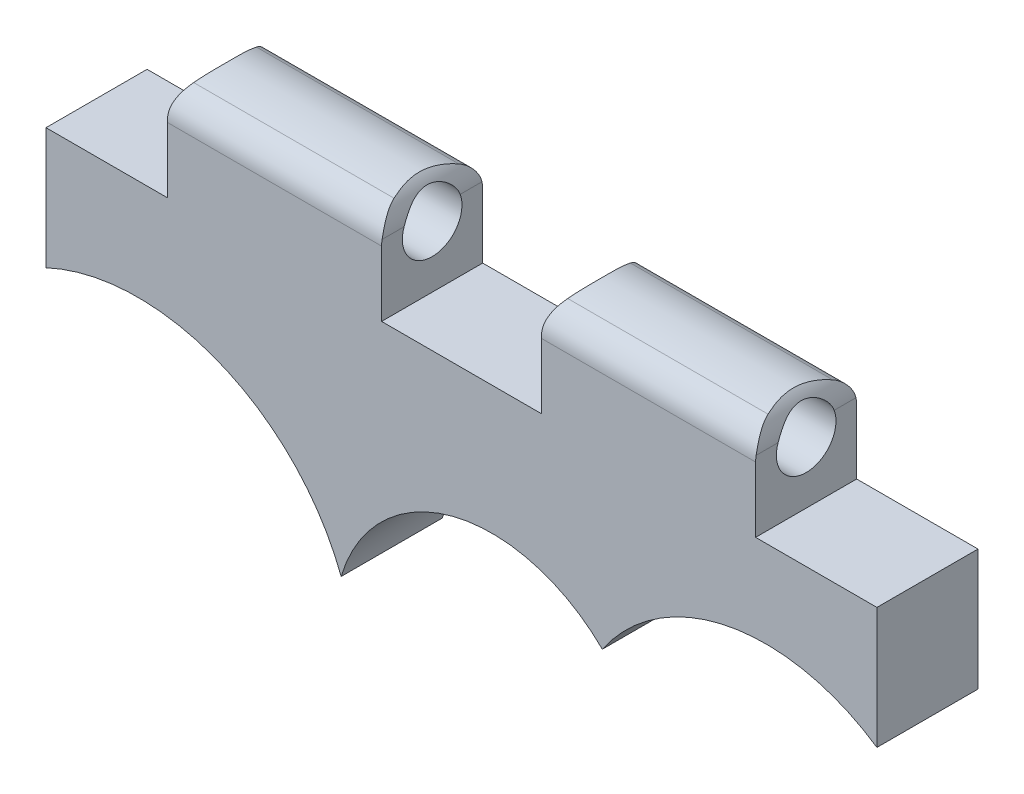
SolidWorks part; units mm, degrees
ref_plane "Alzado" through (0, 0, 0) normal (0, 0, 1) x (1, 0, 0)
ref_plane "Planta" through (0, 0, 0) normal (0, 1, 0) x (1, 0, 0)
ref_plane "Vista lateral" through (0, 0, 0) normal (1, 0, 0) x (0, 0, -1)
sketch "Croquis1" plane through (0, 0, 0) normal (0, 0, 1) x (1, 0, 0)
  line L0 (-11.2351, -0.5) -> (-5.2351, -0.5)
  line L1 (-5.2351, -0.5) -> (-5.2351, 3)
  line L2 (-3.2351, 5) -> (3.3649, 5)
  line L3 (5.3649, 3) -> (5.3649, -0.5)
  line L4 (5.3649, -0.5) -> (13.2649, -0.5)
  line L5 (13.2649, -0.5) -> (13.2649, 3)
  line L6 (15.2649, 5) -> (21.8649, 5)
  line L7 (23.8649, 3) -> (23.8649, -0.5)
  line L8 (23.8649, -0.5) -> (29.8649, -0.5)
  line L9 (29.8649, -0.5) -> (29.8649, -6.5)
  line L19 (-11.2351, -6.5) -> (-11.2351, -0.5)
  arc A0 (-5.2351, 3) -> (-3.2351, 5) centre (-3.2351, 3) cw
  arc A1 (3.3649, 5) -> (5.3649, 3) centre (3.3649, 3) cw
  arc A2 (13.2649, 3) -> (15.2649, 5) centre (15.2649, 3) cw
  arc A3 (21.8649, 5) -> (23.8649, 3) centre (21.8649, 3) cw
  arc A5 (-11.2351, -6.5) -> (3.3649, -12.4262) centre (-6.688, -16.2452) cw
  arc A6 (3.3649, -12.4262) -> (16.2839, -9.0837) centre (10.8239, -14.6179) cw
  arc A7 (16.2839, -9.0837) -> (29.8649, -6.5) centre (24.3662, -14.5824) cw
  dimension "D14" = 2
  dimension "D15" = 2
  dimension "D16" = 2
  dimension "D17" = 2
  dimension "D1" = 6
  dimension "D2" = 3.5
  dimension "D3" = 3.5
  dimension "D4" = 3.5
  dimension "D5" = 3.5
  dimension "D7" = 6
  dimension "D10" = 7.9
  dimension "D11" = 6
  dimension "D12" = 6
extrude "Saliente-Extruir1" add sketch "Croquis1" along normal blind 5
sketch "Croquis5" plane through (23.8649, 0, 0) normal (1, 0, 0) x (0, 0, -1)
  line L0 (0, 55) -> (0, -55) construction
  line L1 (-5, 5) -> (0, 5) construction
  circle A0 centre (-2.5, 2.5) radius 1.475
  dimension "D1" = 2.95
  dimension "D2" = 2.5
  dimension "D3" = 2.5
extrude "Cortar-Extruir3" cut sketch "Croquis5" against normal blind 10.6
sketch "Croquis10" plane through (5.3649, 0, 0) normal (1, 0, 0) x (0, 0, -1)
  line L0 (-5, 5) -> (0, 5) construction
  line L1 (-5, -0.5) -> (-5, 3) construction
  circle A0 centre (-2.5, 2.5) radius 1.475
  dimension "D1" = 2.95
  dimension "D2" = 2.5
  dimension "D3" = 2.5
extrude "Cortar-Extruir5" cut sketch "Croquis10" against normal through all
sketch "Croquis12" plane through (23.8649, 0, 0) normal (1, 0, 0) x (0, 0, -1)
  arc A0 (-5.4661, 3.1974) -> (0.3433, 3.1974) centre (-2.5614, 0.2926) cw
extrude "Cortar-Extruir6" cut sketch "Croquis12" against normal through all and the other way through all
fillet "Redondeo5" radius 1.5 4 edges at (0.0649, 3.5042, 0) (18.5649, 3.5042, 0) (0.0649, 3.5984, 5) (18.5649, 3.5984, 5)
